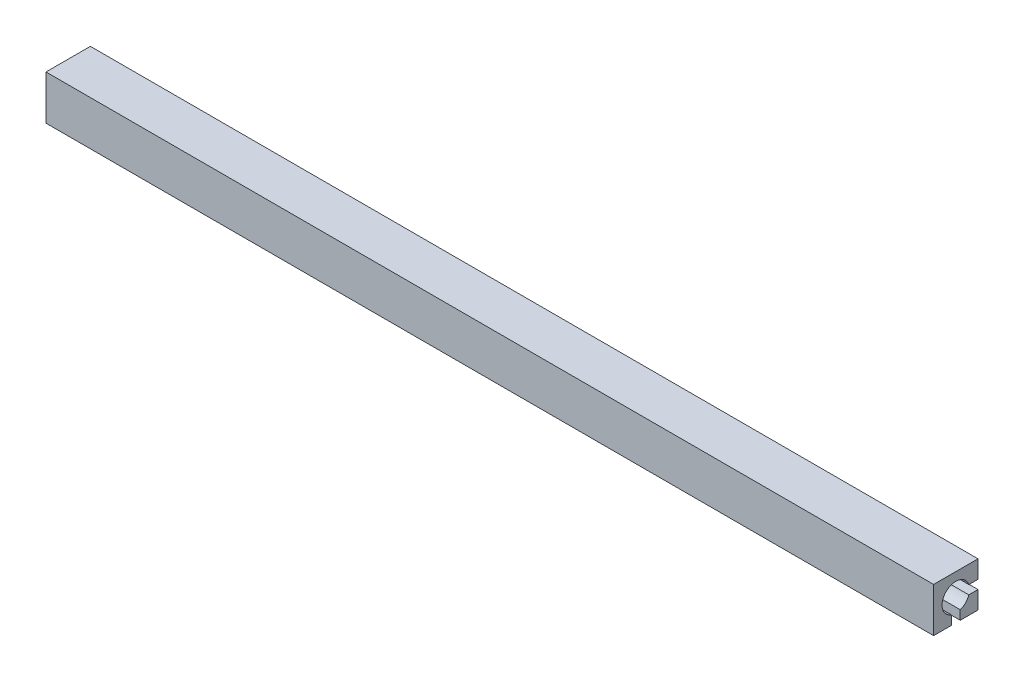
SolidWorks part; units mm, degrees
note: '?' marks a value the reader was unsure of.
ref_plane "Alzado" through (0, 0, 0) normal (0, 0, 1) x (1, 0, 0)
ref_plane "Planta" through (0, 0, 0) normal (0, 1, 0) x (1, 0, 0)
ref_plane "Vista lateral" through (0, 0, 0) normal (1, 0, 0) x (0, 0, -1)
sketch "Croquis1" plane through (0, 0, 0) normal (0, 0, 1) x (1, 0, 0)
  line L0 (5, -10) -> (5, 0) construction
  line L1 (0, 0) -> (10, 0)
  line L2 (0, 0) -> (0, -10)
  line L3 (0, -10) -> (10, -10)
  line L4 (10, 0) -> (10, -10)
  line L6 (10, -5) -> (0, -5) construction
  line L7 (4, -10) -> (6, -10)
  line L8 (4, -10) -> (4, -8)
  line L9 (4, -8) -> (6, -8)
  line L10 (6, -10) -> (6, -8)
  line L11 (10, 0) -> (210, 0)
  line L12 (10, 0) -> (10, -10)
  line L13 (10, -10) -> (210, -10)
  line L14 (210, 0) -> (210, -10)
  dimension "D1" = 10
  dimension "D2" = 10
  dimension "D3" = 2
  dimension "D4" = 1
  dimension "D5" = 2
  dimension "D6" = 200
sketch "Croquis2" plane through (0, 0, 0) normal (0, 0, 1) x (1, 0, 0)
  line L0 (10, -10) -> (10, -210)
  line L1 (0, 0) -> (220, 0)
  line L2 (0, 0) -> (0, -220)
  line L3 (0, -220) -> (220, -220)
  line L4 (220, 0) -> (220, -220)
  line L5 (10, -210) -> (210, -210)
  line L6 (210, -10) -> (210, -210)
  line L7 (10, -10) -> (210, -10)
  dimension "D1" = 220
  dimension "D2" = 220
  dimension "D3" = 10
extrude "Saliente-Extruir1" add sketch "Croquis2" along normal blind 10
sketch "Croquis3" plane through (0, 0, 10) normal (0, 0, 1) x (1, 0, 0)
  line L0 (0, -220) -> (10, -210) construction
  line L1 (10, -210) -> (210, -210) construction
  line L2 (220, 0) -> (210, -10) construction
  line L3 (216, -4) -> (216, -216)
  line L4 (215, -5) -> (5, -5)
  line L5 (215, -5) -> (215, -215)
  line L6 (215, -215) -> (5, -215)
  line L7 (5, -5) -> (5, -215)
  line L8 (216, -216) -> (4, -216)
  line L9 (4, -4) -> (4, -216)
  line L10 (216, -4) -> (4, -4)
  line L11 (214, -6) -> (214, -214)
  line L12 (214, -214) -> (6, -214)
  line L13 (6, -6) -> (6, -214)
  line L14 (214, -6) -> (6, -6)
  dimension "D1" = 1
  dimension "D2" = 1
extrude "Cortar-Extruir1" cut sketch "Croquis3" against normal blind 3.5 contours L3 L10 L9 L8 L7 L4 L5 L6 | L4 L7 L6 L5 L14 L11 L12 L13
sketch "Croquis4" plane through (0, 0, 10) normal (0, 0, 1) x (1, 0, 0)
  line L1 (0, 0) -> (10, 0)
  line L2 (0, 0) -> (0, -10)
  line L3 (0, -10) -> (10, -10)
  line L4 (10, 0) -> (10, -10)
  line L5 (220, 0) -> (210, 0)
  line L6 (220, 0) -> (220, -10)
  line L7 (220, -10) -> (210, -10)
  line L8 (210, 0) -> (210, -10)
  line L9 (210, -210) -> (220, -210)
  line L10 (210, -210) -> (210, -220)
  line L11 (210, -220) -> (220, -220)
  line L12 (220, -210) -> (220, -220)
  line L13 (10, -210) -> (0, -210)
  line L14 (10, -210) -> (10, -220)
  line L15 (10, -220) -> (0, -220)
  line L16 (0, -210) -> (0, -220)
extrude "Saliente-Extruir2" add sketch "Croquis4" along normal blind 200 and the other way blind 10
sketch "Croquis6" plane through (0, 0, 210) normal (0, 0, 1) x (1, 0, 0)
  line L1 (4, -10) -> (6, -10)
  line L2 (4, -10) -> (4, -6.5)
  line L3 (4, -6.5) -> (6, -6.5)
  line L4 (6, -10) -> (6, -6.5)
  line L5 (10, -4) -> (6.5, -4)
  line L6 (10, -4) -> (10, -6)
  line L7 (10, -6) -> (6.5, -6)
  line L8 (6.5, -4) -> (6.5, -6)
  line L9 (0, -220) -> (10, -220)
  line L10 (0, -220) -> (0, -210)
  line L11 (0, -210) -> (10, -210)
  line L12 (10, -220) -> (10, -210)
  line L13 (4, -210) -> (6, -210)
  line L14 (4, -210) -> (4, -213.5)
  line L15 (4, -213.5) -> (6, -213.5)
  line L16 (6, -210) -> (6, -213.5)
  line L17 (10, -214) -> (6.5, -214)
  line L18 (10, -214) -> (10, -216)
  line L19 (10, -216) -> (6.5, -216)
  line L20 (6.5, -214) -> (6.5, -216)
  line L21 (220, 0) -> (210, 0)
  line L22 (220, 0) -> (220, -10)
  line L23 (220, -10) -> (210, -10)
  line L24 (210, 0) -> (210, -10)
  line L25 (210, -4) -> (213.5, -4)
  line L26 (210, -4) -> (210, -6)
  line L27 (210, -6) -> (213.5, -6)
  line L28 (213.5, -4) -> (213.5, -6)
  line L29 (214, -10) -> (216, -10)
  line L30 (214, -10) -> (214, -6.5)
  line L31 (214, -6.5) -> (216, -6.5)
  line L32 (216, -10) -> (216, -6.5)
  line L33 (210, -210) -> (220, -210)
  line L34 (210, -210) -> (210, -220)
  line L35 (210, -220) -> (220, -220)
  line L36 (220, -210) -> (220, -220)
  line L37 (216, -210) -> (214.0019, -210)
  line L38 (216, -210) -> (216, -213.5)
  line L39 (216, -213.5) -> (214.0019, -213.5)
  line L40 (214.0019, -210) -> (214.0019, -213.5)
  line L41 (210, -214) -> (213.5, -214)
  line L42 (210, -214) -> (210, -216)
  line L43 (210, -216) -> (213.5, -216)
  line L44 (213.5, -214) -> (213.5, -216)
  line M3 (0, -10) -> (10, -10)
  line M4 (10, -10) -> (10, 0)
  dimension "D1" = 3.5
  dimension "D2" = 3.5
  dimension "D3" = 3.5
  dimension "D4" = 3.5
  dimension "D5" = 3.5
  dimension "D6" = 3.5
  dimension "D7" = 3.5
  dimension "D8" = 3.5
extrude "Cortar-Extruir2" cut sketch "Croquis6" against normal blind 203.5 contours L5 L8 L7 M4 | L4 L3 L2 M3 | L28 L25 L24 L27 | L23 L32 L31 L30 | L44 L41 L34 L43 | L33 L40 L39 L38 | L16 L11 L14 L15 | L17 L20 L19 L12
sketch "Croquis7" plane through (0, 0, 210) normal (0, 0, 1) x (1, 0, 0)
  line L1 (0, 0) -> (220, 0)
  line L2 (0, 0) -> (0, -220)
  line L3 (0, -220) -> (220, -220)
  line L4 (220, 0) -> (220, -220)
  line L5 (10, -10) -> (210, -10)
  line L6 (10, -10) -> (10, -210)
  line L7 (10, -210) -> (210, -210)
  line L8 (210, -10) -> (210, -210)
extrude "Saliente-Extruir3" add sketch "Croquis7" along normal blind 10
sketch "Croquis8" plane through (0, -210, 0) normal (0, 1, 0) x (1, 0, 0)
  line L0 (210, -210) -> (220, -220) construction
  line L1 (0, -220) -> (10, -210) construction
  line L2 (6.5, -215) -> (213.5, -215) construction
  line L3 (6.5, -216) -> (213.5, -216)
  line L4 (6.5, -214) -> (213.5, -214)
  line L5 (6.5, -214) -> (6.5, -216)
  line L6 (10, -220) -> (10, -210) construction
  line L7 (5, -214) -> (215, -214) construction
  line L8 (5, -215) -> (215, -215) construction
  line L9 (5, -216) -> (215, -216) construction
  line L10 (213.5, -214) -> (213.5, -216)
  line L11 (210, -220) -> (210, -210) construction
  dimension "D3" = 3.5
  dimension "D4" = 3.5
  dimension "D1" = 1
  dimension "D2" = 1
extrude "Cortar-Extruir3" cut sketch "Croquis8" against normal blind 3.5 and the other way blind 203.5 contours L4 L10 L3 L5
ref_plane "PlanoX" through (0, 0, 110) normal (0, 0, 1) x (1, 0, 0)
ref_plane "PlanoY" through (0, -110, 0) normal (0, 1, 0) x (1, 0, 0)
ref_plane "PlanoZ" through (110, 0, 0) normal (1, 0, 0) x (0, 0, -1)
ref_axis "EjeXY" through (-11, -110, 110) along (1, 0, 0)?
ref_axis "EjeYZ" through (110, -110, -11) along (0, 0, 1)?
ref_axis "EjeXZ" through (110, 11, 110) along (0, -1, 0)?
pattern_circular "MatrizC1" count 4 over 360 about axis through (0, -110, 110) along (1, 0, 0) of "Cortar-Extruir3"
sketch "Croquis9" plane through (0, 0, 220) normal (0, 0, 1) x (1, 0, 0)
  line L0 (0, -110) -> (220, -110) construction
  line L1 (0, 0) -> (0, -220) construction
  line L2 (220, -220) -> (220, 0) construction
  line L3 (0, -118) -> (220, -118)
  line L4 (0, -102) -> (220, -102)
  line L5 (0, -102) -> (0, -118)
  line L6 (220, -118) -> (220, -102)
  line L7 (71.8015, -110) -> (75, -110) construction
  line L8 (71.8015, -107.75) -> (75, -107.75)
  line L9 (71.8015, -112.25) -> (75, -112.25)
  line L10 (86, -102) -> (86, -118)
  line L11 (110, -121) -> (110, 121) construction
  line L12 (134, -102) -> (134, -118)
  line L13 (148.1985, -110) -> (145, -110) construction
  line L14 (148.1985, -107.75) -> (145, -107.75)
  line L15 (148.1985, -112.25) -> (145, -112.25)
  arc A0 (71.8015, -107.75) -> (71.8015, -112.25) centre (71.8015, -110) ccw
  arc A1 (75, -112.25) -> (75, -107.75) centre (75, -110) ccw
  arc A2 (148.1985, -107.75) -> (148.1985, -112.25) centre (148.1985, -110) cw
  arc A3 (145, -112.25) -> (145, -107.75) centre (145, -110) cw
  point P12 (73.4008, -110)
  point P17 (110, -110)
  point P26 (146.5992, -110)
  dimension "D1" = 35
  dimension "D2" = 4.5
  dimension "D3" = 86
extrude "Brazos" add sketch "Croquis9" against normal blind 10 contours L10 L4 L7 L3 A1 L9 A0 L8 | L4 A1 L3 L7 | L4 L12 L3 L15 A3 L14 A2 | L4 L12 L3 L10
pattern_circular "MatrizC2" count 4 over 360 about axis through (110, 0, 110) along (0, 1, 0) of "Cortar-Extruir3"
sketch "Croquis10" plane through (0, 0, 0) normal (0, 1, 0) x (1, 0, 0)
  line L1 (210, -210) -> (-54.6139, -210)
  line L3 (210, 5.7303) -> (-54.6139, 5.7303)
  line L4 (-54.6139, -210) -> (-54.6139, 5.7303)
  line L5 (210, 5.7303) -> (296.6998, 5.7303)
  line L7 (210, -210) -> (296.6998, -210)
  line L8 (296.6998, 5.7303) -> (296.6998, -210)
extrude "Cortar-Extruir4" cut sketch "Croquis10" against normal through all
sketch "Croquis11" plane through (0, 0, 220) normal (0, 0, 1) x (1, 0, 0)
  line L0 (225.3482, -10) -> (300.0187, -10)
  line L1 (10, -10) -> (210, -10)
  line L3 (10, -229.853) -> (300.0187, -229.853)
  line L4 (300.0187, -10) -> (300.0187, -229.853)
  line L5 (-6.5209, -10) -> (-53.6508, -10)
  line L7 (10, -229.853) -> (-53.6508, -229.853)
  line L8 (-53.6508, -10) -> (-53.6508, -229.853)
  line L10 (10, -10) -> (10, 9.0796)
  line L11 (10, 9.0796) -> (-6.5209, 9.0796)
  line L12 (-6.5209, -10) -> (-6.5209, 9.0796)
  line L14 (210, -10) -> (210, 9.8728)
  line L15 (210, 9.8728) -> (225.3482, 9.8728)
  line L16 (225.3482, -10) -> (225.3482, 9.8728)
extrude "Cortar-Extruir6" cut sketch "Croquis11" against normal through all
sketch "Croquis12" plane through (10, 0, 0) normal (-1, 0, 0) x (0, 0, 1)
  line L0 (210, 0) -> (220, -10) construction
  circle A0 centre (215, -5) radius 3.1
  dimension "D1" = 6.2
extrude "Cortar-Extruir7" cut sketch "Croquis12" against normal blind 10.2
sketch "Croquis13" plane through (210, 0, 0) normal (1, 0, 0) x (0, 0, -1)
  line L0 (-220, 0) -> (-210, -10) construction
  circle A0 centre (-215, -5) radius 3.1
  dimension "D1" = 6.2
extrude "Cortar-Extruir8" cut sketch "Croquis13" against normal blind 10.2
